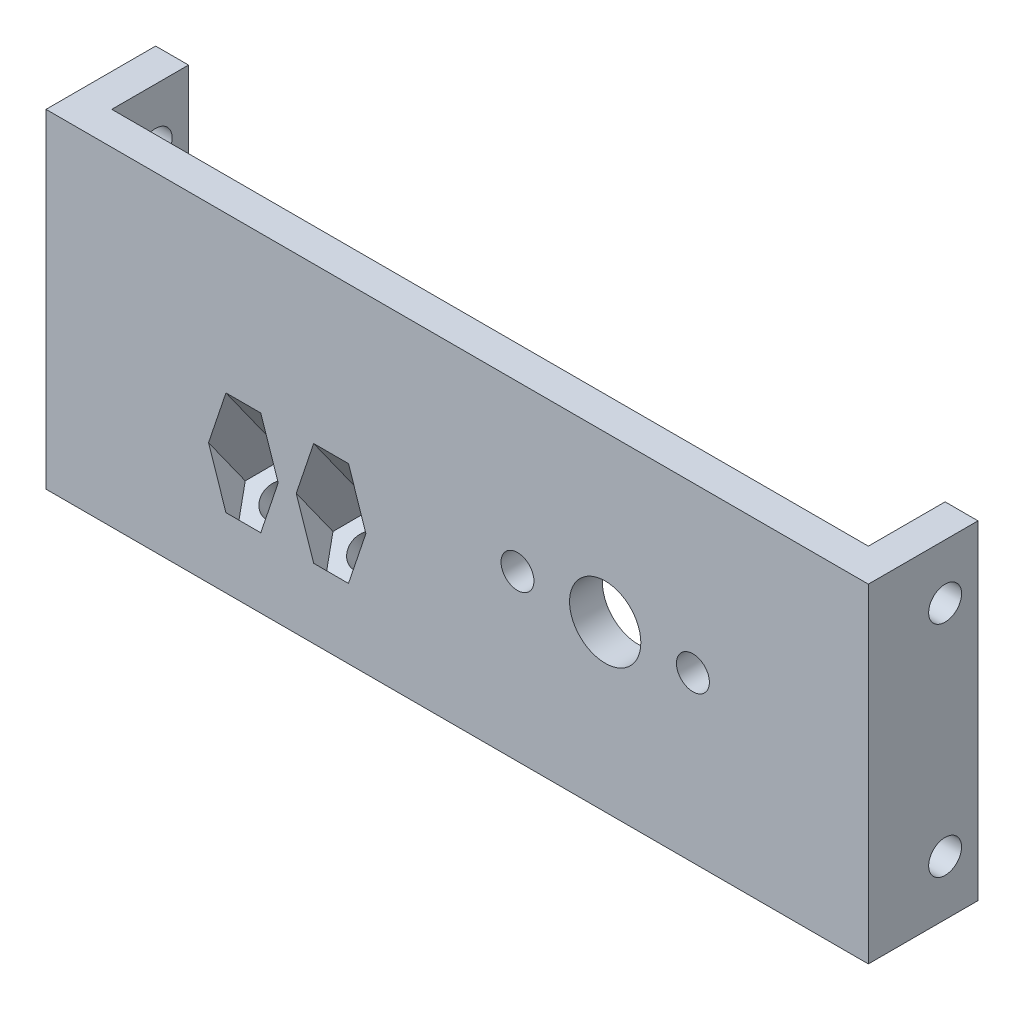
SolidWorks part; units mm, degrees
ref_plane "Front Plane" through (0, 0, 0) normal (0, 0, 1) x (1, 0, 0)
ref_plane "Top Plane" through (0, 0, 0) normal (0, 1, 0) x (1, 0, 0)
ref_plane "Right Plane" through (0, 0, 0) normal (1, 0, 0) x (0, 0, -1)
sketch "Sketch1" plane through (0, 0, 0) normal (0, 0, 1) x (1, 0, 0)
  line L1 (-37.5, -15) -> (37.5, -15)
  line L2 (-37.5, -15) -> (-37.5, 15)
  line L3 (-37.5, 15) -> (37.5, 15)
  line L4 (37.5, -15) -> (37.5, 15)
  line L5 (-37.5, -15) -> (37.5, 15) construction
  line L6 (-37.5, 15) -> (37.5, -15) construction
  point P0 (0, 0)
  dimension "D1" = 30
  dimension "D2" = 75
extrude "Boss-Extrude1" add sketch "Sketch1" along normal blind 3
sketch "Sketch2" plane through (0, 0, 0) normal (0, 0, -1) x (-1, 0, 0)
  line L0 (-37.5, -15) -> (-37.5, 15) construction
  line L1 (-34.5, -15) -> (-37.5, -15)
  line L2 (-34.5, -15) -> (-34.5, 15)
  line L3 (-34.5, 15) -> (-37.5, 15)
  line L4 (-37.5, -15) -> (-37.5, 15)
  line L5 (-34.5, -15) -> (-37.5, 15) construction
  line L6 (-34.5, 15) -> (-37.5, -15) construction
  line L7 (-37.5, 15) -> (37.5, 15) construction
  line L8 (37.5, -15) -> (-37.5, -15) construction
  point P0 (-36, 0)
  dimension "D1" = 0
  dimension "D2" = 0
  dimension "D3" = 3
extrude "Boss-Extrude2" add sketch "Sketch2" along normal blind 7
sketch "Sketch4" plane through (34.5, 0, 0) normal (-1, 0, 0) x (0, 0, 1)
  line L0 (-7, 15) -> (0, 15) construction
  line L1 (-7, -15) -> (-7, 15) construction
  circle A0 centre (-4, 10) radius 1.5
  dimension "D1" = 3
  dimension "D2" = 5
  dimension "D3" = 3
extrude "Cut-Extrude1" cut sketch "Sketch4" against normal blind 3
mirror "Mirror2" about plane through (0, 0, 0) normal (0, 1, 0) of "Cut-Extrude1"
mirror "Mirror1" about plane through (0, 0, 0) normal (1, 0, 0) of "Mirror2", "Cut-Extrude1", "Boss-Extrude2"
sketch "Sketch5" plane through (0, 0, 3) normal (0, 0, 1) x (1, 0, 0)
  line L0 (37.5, -15) -> (37.5, 15) construction
  line L1 (37.5, 15) -> (-37.5, 15) construction
  circle A0 centre (13.5, 0) radius 3.25
  circle A1 centre (5.5, 0) radius 1.5
  circle A2 centre (21.5, 0) radius 1.5
  dimension "D1" = 3
  dimension "D2" = 3
  dimension "D3" = 6.5
  dimension "D4" = 8
  dimension "D5" = 8
  dimension "D6" = 16
  dimension "D7" = 15
extrude "Cut-Extrude2" cut sketch "Sketch5" against normal blind 10
sketch "Sketch6" plane through (0, -15, 0) normal (0, -1, 0) x (1, 0, 0)
  line L0 (-37.5, 3) -> (37.5, 3) construction
  line L1 (-23.5, 3) -> (-7.5, 3)
  line L2 (-23.5, 3) -> (-23.5, -7)
  line L3 (-23.5, -7) -> (-7.5, -7)
  line L4 (-7.5, 3) -> (-7.5, -7)
  line L5 (-34.5, -7) -> (-34.5, 0) construction
  dimension "D1" = 0
  dimension "D2" = 11
  dimension "D3" = 16
extrude "Boss-Extrude3" add sketch "Sketch6" against normal blind 8
chamfer "Chamfer1" distance 5 distance2 7 1 edges at (-15.5, -15, -7) first distance on face at (-15.5, -11, -7)
sketch "Sketch7" plane through (0, -9.9324, -7.0946) normal (0, -0.8137, -0.5812) x (1, 0, 0)
  line L0 (-23.5, 8.7186) -> (-23.5, 4.0687) construction
  line L1 (-7.5, 4.0687) -> (-7.5, 8.7186) construction
  line L2 (-23.5, 8.7186) -> (-7.5, 8.7186) construction
  circle A0 centre (-19.5, 4.7186) radius 1.5
  circle A1 centre (-11.5, 4.7186) radius 1.5
  dimension "D1" = 3
  dimension "D2" = 3
  dimension "D3" = 4
  dimension "D4" = 4
  dimension "D5" = 4
  dimension "D6" = 4
extrude "Cut-Extrude3" cut sketch "Sketch7" against normal blind 5
chamfer "Chamfer2" distance 5 angle 45 1 edges at (-15.5, -7, 0)
chamfer "Chamfer3" distance 2 angle 45 1 edges at (-15.5, -7, -7)
sketch "Sketch9" plane through (0, -9.9324, -7.0946) normal (0, -0.8137, -0.5812) x (1, 0, 0)
  line L1 (-16.3246, 4.7186) -> (-17.9123, 7.4686)
  line L2 (-17.9123, 7.4686) -> (-21.0877, 7.4686)
  line L3 (-21.0877, 7.4686) -> (-22.6754, 4.7186)
  line L4 (-22.6754, 4.7186) -> (-21.0877, 1.9686)
  line L5 (-21.0877, 1.9686) -> (-17.9123, 1.9686)
  line L6 (-17.9123, 1.9686) -> (-16.3246, 4.7186)
  line L7 (-8.3246, 4.7186) -> (-9.9123, 7.4686)
  line L8 (-9.9123, 7.4686) -> (-13.0877, 7.4686)
  line L9 (-13.0877, 7.4686) -> (-14.6754, 4.7186)
  line L10 (-14.6754, 4.7186) -> (-13.0877, 1.9686)
  line L11 (-13.0877, 1.9686) -> (-9.9123, 1.9686)
  line L12 (-9.9123, 1.9686) -> (-8.3246, 4.7186)
  circle A0 centre (-19.5, 4.7186) radius 2.75 construction
  circle A1 centre (-11.5, 4.7186) radius 2.75 construction
  dimension "D1" = 5.5
  dimension "D2" = 5.5
extrude "Cut-Extrude4" cut sketch "Sketch9" against normal through all from offset 5 offset against normal yes
equation "\"D2@Sketch7\"=\"D1@Sketch7\""
equation "\"D5@Sketch7\"=4"
